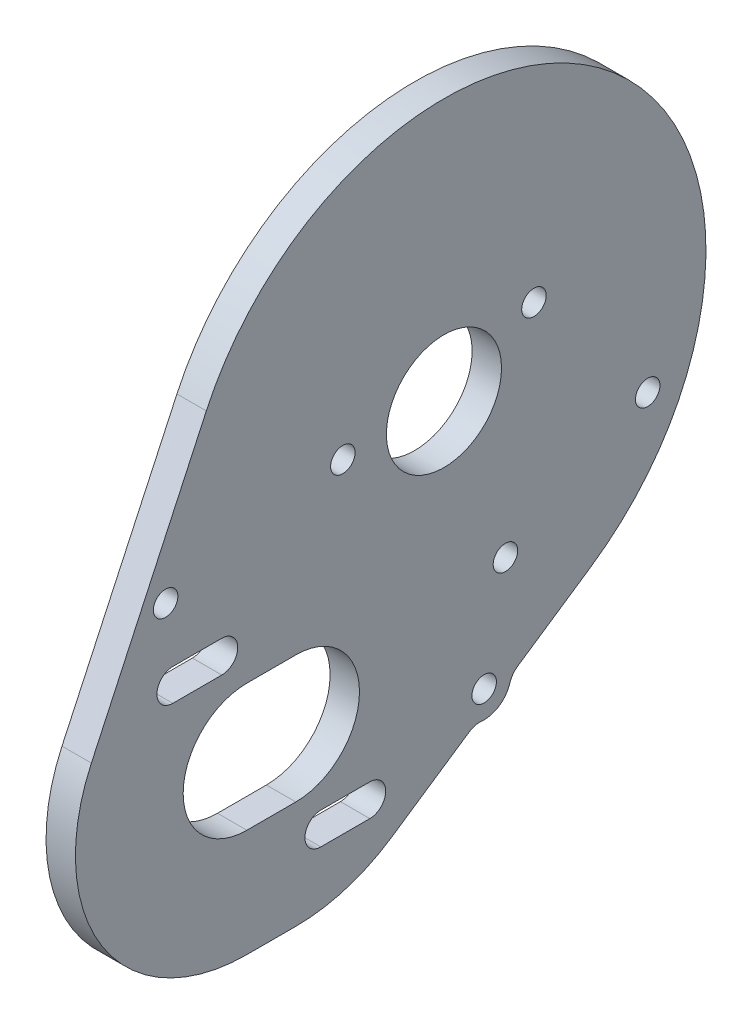
SolidWorks part; units mm, degrees
ref_plane "Front Plane" through (0, 0, 0) normal (0, 0, 1) x (1, 0, 0)
ref_plane "Top Plane" through (0, 0, 0) normal (0, 1, 0) x (1, 0, 0)
ref_plane "Right Plane" through (0, 0, 0) normal (1, 0, 0) x (0, 0, -1)
sketch "Sketch3" plane through (0, 0, 0) normal (1, 0, 0) x (0, 0, -1)
  line L0 (-20.125, -14.875) -> (-15.125, -14.875)
  line L1 (-15.125, -27.875) -> (-20.125, -27.875)
  line L2 (-26.625, -21.375) -> (-26.625, -12.1581) construction
  line L3 (-8.625, -21.375) -> (-8.625, -10.4698) construction
  line L4 (0, -5.875) -> (9.1895, -5.875) construction
  line L5 (-5.875, 0) -> (-5.875, 7.7787) construction
  line L6 (-24.2616, 11.2667) -> (-35.997, -14.0042)
  line L7 (-20.125, -38.875) -> (-15.125, -38.875)
  line L8 (14.9701, -22.1689) -> (7.5344, -27.19)
  line L9 (-37.625, -21.375) -> (-37.625, -11.278) construction
  line L10 (-22.6794, -9.625) -> (-27.6794, -9.625)
  line L11 (-27.6794, -12.875) -> (-22.6794, -12.875)
  line L12 (-7.5706, -29.875) -> (-12.5706, -29.875)
  line L13 (-12.5706, -33.125) -> (-7.5706, -33.125)
  line L14 (-12.5706, -31.5) -> (-27.6794, -11.25) construction
  line L15 (2.5524, -30.5542) -> (-5.3315, -35.878)
  circle A0 centre (0, 0) radius 5.875
  circle A1 centre (-20.125, -21.375) radius 6.5
  circle A2 centre (-15.125, -21.375) radius 6.5
  circle A3 centre (0, 0) radius 26.75
  arc A4 (-35.997, -14.0042) -> (-20.125, -38.875) centre (-20.125, -21.375) ccw
  arc A5 (-15.125, -38.875) -> (-5.3315, -35.878) centre (-15.125, -21.375) ccw
  circle A6 centre (-22.6794, -11.25) radius 1.625
  circle A7 centre (-27.6794, -11.25) radius 1.625
  circle A8 centre (-12.5706, -31.5) radius 1.625
  circle A9 centre (-7.5706, -31.5) radius 1.625
  circle A10 centre (-28.418, -3.6558) radius 1.25
  circle A11 centre (-10.3226, 0) radius 1.25
  circle A12 centre (9.1895, 4.1401) radius 1.25
  circle A13 centre (20.8005, -9.625) radius 1.25
  circle A14 centre (6.2776, -16.9583) radius 1.25
  circle A15 centre (4.1043, -27.4815) radius 1.25
  arc A16 (3.8538, -30.22) -> (6.7381, -28.2723) centre (4.1043, -27.4815) ccw
  arc A17 (2.5524, -30.5542) -> (3.8538, -30.22) centre (3.6716, -32.2117) cw
  arc A18 (6.7381, -28.2723) -> (7.5344, -27.19) centre (8.6536, -28.8475) cw
  point P62 (3.2378, -30.0914)
  dimension "D1" = 11.75
  dimension "D6" = 53.5
  dimension "D8" = 11
  dimension "D9" = 17.5
  dimension "D15" = 2.5
  dimension "D17" = 2.5
  dimension "D18" = 2.5
  dimension "D19" = 2.5
  dimension "D20" = 2.5
  dimension "D21" = 2.5
  dimension "D4" = 1.5
  dimension "D10" = 2
  dimension "D2" = 18
  dimension "D3" = 5
  dimension "D5" = 2.75
  dimension "D7" = 5
  dimension "D11" = 5
  dimension "D13" = 3.25
  dimension "D14" = 3.25
  dimension "D16" = 5
extrude "Boss-Extrude2" add sketch "Sketch3" along normal blind 3 separate body contours A15 A3 A2 A1 L11 A7 L10 L6 A4 L7 A5 L8 A10 A9 L13 A8 L12 | A15 A3 L10 A6 L11 A1 A2 A14 A13 A12 A11 A0 region at (0, -14.1992, 21.2046) region at (0, -22.4501, 27.2712)
ref_plane "Plane1" through (0, -21.375, 0) normal (0, 1, 0) x (1, 0, 0)
ref_plane "Plane2" through (0, -11.25, 0) normal (0, 1, 0) x (-1, 0, 0)
